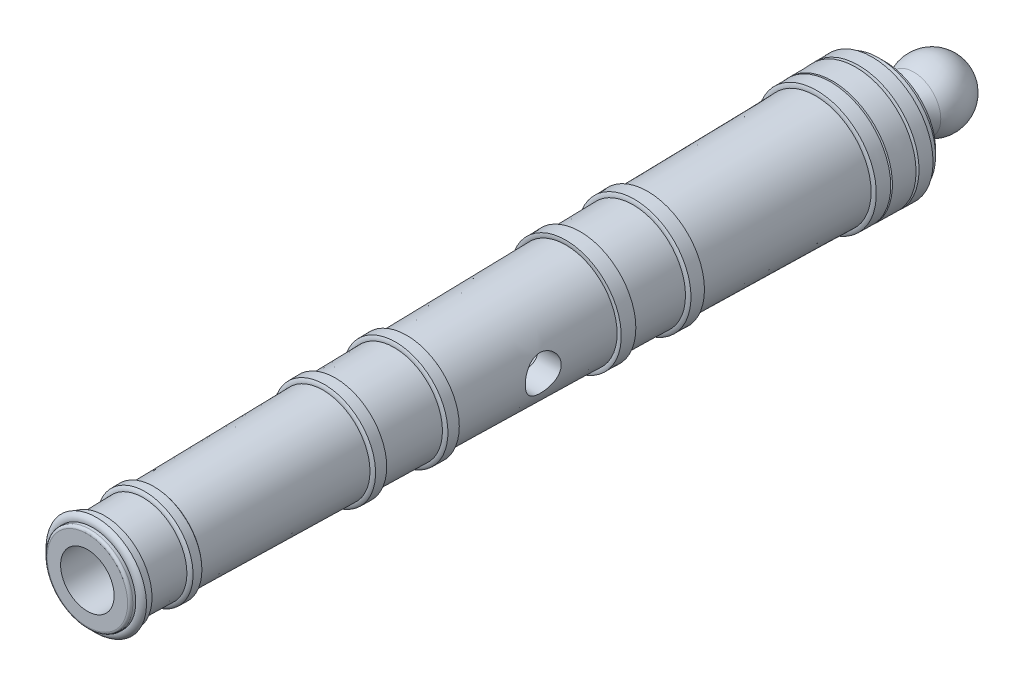
SolidWorks part; units mm, degrees
material "Brass"
ref_plane "Front Plane" through (0, 0, 0) normal (0, 0, 1) x (1, 0, 0)
ref_plane "Top Plane" through (0, 0, 0) normal (0, 1, 0) x (1, 0, 0)
ref_plane "Right Plane" through (0, 0, 0) normal (1, 0, 0) x (0, 0, -1)
sketch "Sketch1" plane through (0, 0, 0) normal (0, 0, 1) x (1, 0, 0)
  circle A0 centre (0, 0) radius 10.16
  dimension "D1" = 20.32
extrude "Boss-Extrude1" add sketch "Sketch1" along normal mid plane 192.532
draft "Draft1" type of draft neutral plane draft angle 1 faces to draft 1 face at (10.16, 0, 96.266) neutral plane through (0, 0, 96.266) neutral plane normal (0, 0, 1) parameters "D1"=1
ref_plane "Plane1" through (0, 0, 93.472) normal (0, 0, 1) x (1, 0, 0)
sketch "Sketch2" plane through (0, 0, 93.472) normal (0, 0, 1) x (1, 0, 0)
  circle A0 centre (0, 0) radius 10.16
  circle A1 centre (0, 0) radius 10.16 construction
  dimension "D1" = 20.32
sketch "Sketch3" plane through (0, 0, 0) normal (0, 1, 0) x (1, 0, 0)
  line L0 (-10.16, -93.472) -> (10.16, -93.472) construction
  circle A0 centre (-10.451, -93.472) radius 1.524
  dimension "D1" = 3.048
sweep "Sweep1" add profiles "Sketch3" path "Sketch2"
fillet "Fillet1" radius 0.635 1 edges at (10.16, 0, 96.266)
sketch "Sketch4" plane through (0, 0, 96.266) normal (0, 0, 1) x (1, 0, 0)
  circle A0 centre (0, 0) radius 6.35
  dimension "D1" = 12.7
extrude "Cut-Extrude1" cut sketch "Sketch4" against normal blind 177.8
ref_plane "Plane2" through (0, 0, 81.534) normal (0, 0, 1) x (1, 0, 0)
sketch "Sketch6" plane through (0, 0, 81.534) normal (0, 0, 1) x (1, 0, 0)
  circle A0 centre (0, 0) radius 10.3776
sketch "Sketch7" plane through (0, 0, 0) normal (0, 1, 0) x (1, 0, 0)
  line L0 (-10.3776, -81.534) -> (10.3776, -81.534) construction
  circle A0 centre (-10.272, -81.534) radius 1.524
  dimension "D1" = 3.048
sweep "Sweep2" add profiles "Sketch7" path "Sketch6"
ref_plane "Plane3" through (0, 0, 38.735) normal (0, 0, 1) x (1, 0, 0)
sketch "Sketch8" plane through (0, 0, 38.735) normal (0, 0, 1) x (1, 0, 0)
  circle A0 centre (0, 0) radius 11.176
sketch "Sketch9" plane through (0, 0, 0) normal (0, 1, 0) x (1, 0, 0)
  line L0 (-11.176, -38.735) -> (11.176, -38.735) construction
  circle A0 centre (-11.1211, -38.735) radius 1.651
  dimension "D1" = 3.302
sweep "Sweep3" add profiles "Sketch9" path "Sketch8"
ref_plane "Plane4" through (0, 0, 21.844) normal (0, 0, 1) x (1, 0, 0)
sketch "Sketch10" plane through (0, 0, 21.844) normal (0, 0, 1) x (1, 0, 0)
  circle A0 centre (0, 0) radius 11.3836
sketch "Sketch11" plane through (0, 0, 0) normal (0, 1, 0) x (1, 0, 0)
  line L0 (11.193, -37.0856) -> (13.5207, 96.266) construction
  line L1 (-11.3836, -21.844) -> (11.3836, -21.844) construction
  circle A0 centre (11.459, -21.844) radius 1.651
  dimension "D1" = 3.302
sweep "Sweep4" add profiles "Sketch11" path "Sketch10"
ref_plane "Plane5" through (0, 0, -18.923) normal (0, 0, 1) x (1, 0, 0)
sketch "Sketch12" plane through (0, 0, -18.923) normal (0, 0, 1) x (1, 0, 0)
  circle A0 centre (0, 0) radius 12.1196
sketch "Sketch13" plane through (0, 0, 0) normal (0, 1, 0) x (1, 0, 0)
  line L0 (-12.1196, 18.923) -> (12.1196, 18.923) construction
  circle A0 centre (-12.6336, 18.923) radius 1.778
  dimension "D1" = 3.556
sweep "Sweep5" add profiles "Sketch13" path "Sketch12"
ref_plane "Plane6" through (0, 0, -35.052) normal (0, 0, 1) x (1, 0, 0)
sketch "Sketch14" plane through (0, 0, -35.052) normal (0, 0, 1) x (1, 0, 0)
  circle A0 centre (0, 0) radius 12.446
sketch "Sketch15" plane through (0, 0, 0) normal (0, 1, 0) x (1, 0, 0)
  line L0 (-12.446, 35.052) -> (12.446, 35.052) construction
  circle A0 centre (-12.3582, 35.052) radius 1.905
  dimension "D1" = 3.81
sweep "Sweep6" add profiles "Sketch15" path "Sketch14"
sketch "Sketch16" plane through (0, 0, 0) normal (1, 0, 0) x (0, 0, -1)
  circle A0 centre (0, 0) radius 4.191
  dimension "D1" = 8.382
extrude "Cut-Extrude2" cut sketch "Sketch16" against normal mid plane 25.4
ref_plane "Plane7" through (0, 0, -78.359) normal (0, 0, 1) x (1, 0, 0)
sketch "Sketch17" plane through (0, 0, -78.359) normal (0, 0, 1) x (1, 0, 0)
  circle A0 centre (0, 0) radius 12.7
sketch "Sketch18" plane through (0, 0, 0) normal (0, 1, 0) x (1, 0, 0)
  line L4 (12.4853, 36.9528) -> (13.5207, 96.266) construction
  line L5 (-12.7, 78.359) -> (12.7, 78.359) construction
  circle A0 centre (13.2081, 78.359) radius 1.9431
  dimension "D1" = 3.8862
sweep "Sweep7" add profiles "Sketch18" path "Sketch17"
ref_plane "Plane8" through (0, 0, -83.185) normal (0, 0, 1) x (1, 0, 0)
sketch "Sketch19" plane through (0, 0, -83.185) normal (0, 0, 1) x (1, 0, 0)
  circle A0 centre (0, 0) radius 13.1652
sketch "Sketch20" plane through (0, 0, 0) normal (0, 1, 0) x (1, 0, 0)
  line L0 (-13.5207, 96.266) -> (-13.242, 80.3018) construction
  line L1 (-13.1652, 83.185) -> (13.1652, 83.185) construction
  circle A0 centre (-13.2923, 83.185) radius 2.921
  dimension "D1" = 5.842
sweep "Sweep8" add profiles "Sketch20" path "Sketch19"
ref_plane "Plane9" through (0, 0, -88.265) normal (0, 0, 1) x (1, 0, 0)
sketch "Sketch21" plane through (0, 0, -88.265) normal (0, 0, 1) x (1, 0, 0)
  circle A0 centre (0, 0) radius 13.2607
sketch "Sketch22" plane through (0, 0, 0) normal (0, 1, 0) x (1, 0, 0)
  line L0 (-13.2607, 88.265) -> (13.2607, 88.265) construction
  line L1 (13.3433, 86.1056) -> (13.5207, 96.266) construction
  circle A0 centre (13.381, 88.265) radius 1.905
  dimension "D1" = 3.81
sweep "Sweep9" add profiles "Sketch22" path "Sketch21"
sketch "Sketch24" plane through (0, 0, 0) normal (1, 0, 0) x (0, 0, -1)
  line L0 (-94.0949, 11.1802) -> (103.6135, 14.6312)
  line L1 (17.2147, 12.1408) -> (-20.1933, 11.4879) construction
  line L3 (-94.0949, 11.1802) -> (-94.0949, 19.5418)
  line L4 (-94.0949, 19.5418) -> (103.6135, 22.9928)
  line L5 (103.6135, 22.9928) -> (103.6135, 14.6312)
  dimension "D1" = 197.7084
revolve "Cut-Revolve1" cut sketch "Sketch24" angle 360
sketch "Sketch25" plane through (0, 0, 0) normal (1, 0, 0) x (0, 0, -1)
  line L12 (90.1697, 0) -> (90.1697, 13.4364)
  line L13 (90.1697, 13.4364) -> (91.4397, 13.4364)
  line L14 (96.266, 13.5207) -> (90.1697, 13.4142) construction
  line L15 (91.4397, 13.4364) -> (91.4397, 12.1664)
  line L16 (91.4397, 12.1664) -> (92.7097, 12.1664)
  line L17 (92.7097, 12.1664) -> (92.7097, 10.8964)
  line L18 (92.7097, 10.8964) -> (93.4717, 10.8964)
  line L19 (93.4717, 10.8964) -> (93.4717, 9.6264)
  line L20 (93.4717, 9.6264) -> (93.9797, 9.6264)
  line L21 (93.9797, 9.6264) -> (93.9797, 0)
  line L22 (93.9797, 0) -> (90.1697, 0)
  line L23 (90.1697, 13.4142) -> (90.1697, -13.4142) construction
  dimension "D8" = 1.27
  dimension "D9" = 1.27
  dimension "D10" = 0.762
  dimension "D11" = 0.508
  dimension "D12" = 1.27
  dimension "D13" = 1.27
  dimension "D14" = 1.27
  dimension "D15" = 13.4364
sketch "Sketch30" plane through (0, 0, 0) normal (1, 0, 0) x (0, 0, -1)
  line L0 (90.1697, 13.4364) -> (90.1697, 14.8602)
  line L1 (90.1697, 14.8602) -> (98.0263, 14.8602)
  line L2 (98.0263, 14.8602) -> (98.0263, 0)
  line L3 (77.91, 0) -> (102.216, 0) construction
  line L4 (98.0263, 0) -> (93.9797, 0)
  line L5 (93.9797, 0) -> (93.9797, 9.6264)
  line L6 (93.9797, 9.6264) -> (93.4717, 9.6264)
  line L7 (93.4717, 9.6264) -> (93.4717, 10.8964)
  line L8 (93.4717, 10.8964) -> (92.7097, 10.8964)
  line L9 (92.7097, 10.8964) -> (92.7097, 12.1664)
  line L10 (92.7097, 12.1664) -> (91.4397, 12.1664)
  line L11 (91.4397, 12.1664) -> (91.4397, 13.4364)
  line L12 (91.4397, 13.4364) -> (90.1697, 13.4364)
revolve "Cut-Revolve2" cut sketch "Sketch30" angle 360
sketch "Sketch31" plane through (0, 0, 0) normal (1, 0, 0) x (0, 0, -1)
  line L0 (72.2981, 0) -> (96.4411, 0) construction
  line L1 (96.2657, 0) -> (111.7597, 0)
  line L2 (90.1697, 13.4142) -> (90.1697, -13.4142) construction
  line L3 (96.2657, 0) -> (93.9797, 0)
  line L4 (93.9797, 0) -> (93.9797, 7.747)
  line L5 (93.9797, -9.6264) -> (93.9797, 9.6264) construction
  line L6 (99.6845, 6.4252) -> (94.3923, 2.8602) construction
  line L7 (94.3923, 2.8602) -> (93.9797, 7.747) construction
  arc A0 (111.7597, 0) -> (99.6845, 6.4252) centre (104.0127, 0) ccw
  spline S0 degree 2 poles (99.6845, 6.4252) (94.3923, 2.8602) (93.9797, 7.747) knots 0 0 0 1 1 1
  dimension "D1" = 15.494
  dimension "D2" = 21.59
  dimension "D3" = 7.747
  dimension "D4" = 2.8602
  dimension "D5" = 0.4126
  dimension "D6" = 6.4252
revolve "Revolve1" add sketch "Sketch31" angle 360
